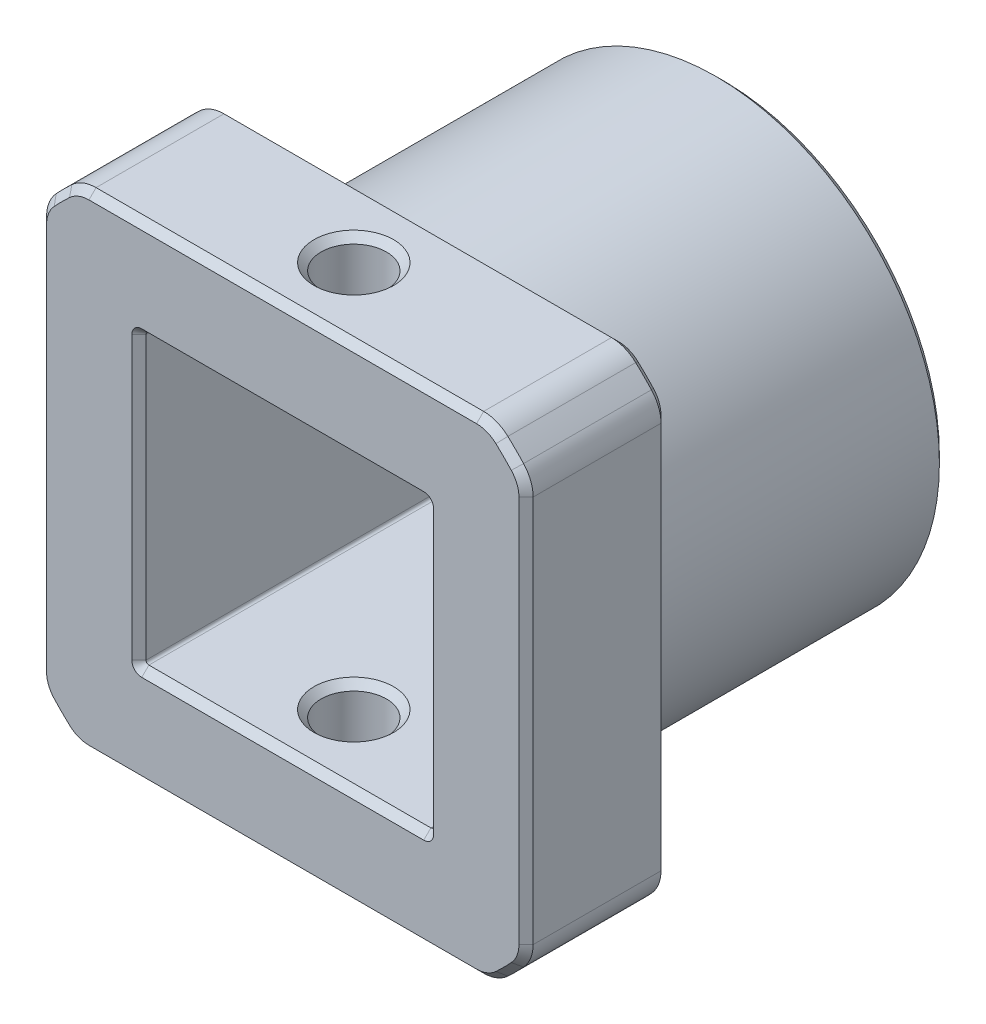
SolidWorks part; units mm, degrees
ref_plane "Front" through (0, 0, 0) normal (0, 0, 1) x (1, 0, 0)
ref_plane "Top" through (0, 0, 0) normal (0, 1, 0) x (1, 0, 0)
ref_plane "Right" through (0, 0, 0) normal (1, 0, 0) x (0, 0, -1)
sketch "Skizze1" plane through (0, 0, 0) normal (0, 0, 1) x (1, 0, 0)
  line L1 (-10.125, -10.125) -> (10.125, -10.125)
  line L2 (-10.125, -10.125) -> (-10.125, 10.125)
  line L3 (-10.125, 10.125) -> (10.125, 10.125)
  line L4 (10.125, -10.125) -> (10.125, 10.125)
  line L5 (-10.125, -10.125) -> (10.125, 10.125) construction
  line L6 (-10.125, 10.125) -> (10.125, -10.125) construction
  circle A0 centre (0, 0) radius 15.725
  point P0 (0, 0)
  dimension "D2" = 31.45
  dimension "D1" = 20.25
extrude "Aufsatz-Linear austragen1" add sketch "Skizze1" along normal blind 21
sketch "Skizze2" plane through (0, 0, 21) normal (0, 0, 1) x (1, 0, 0)
  line L0 (-14.594, 17.125) -> (14.594, 17.125)
  line L1 (-10.125, -10.125) -> (10.125, -10.125)
  line L2 (-10.125, -10.125) -> (-10.125, 10.125)
  line L3 (-10.125, 10.125) -> (10.125, 10.125)
  line L4 (10.125, -10.125) -> (10.125, 10.125)
  line L5 (-10.125, -10.125) -> (10.125, 10.125) construction
  line L6 (-10.125, 10.125) -> (10.125, -10.125) construction
  line L7 (0, 0) -> (13.8508, 0) construction
  line L8 (0, 0) -> (0, 13.2524) construction
  line L9 (17.125, -14.594) -> (17.125, 14.594)
  line L10 (14.594, -17.125) -> (-14.594, -17.125)
  line L11 (-17.125, 14.594) -> (-17.125, -14.594)
  arc A0 (-14.594, 17.125) -> (-17.125, 14.594) centre (0, 0) ccw
  arc A2 (-17.125, -14.594) -> (-14.594, -17.125) centre (0, 0) ccw
  arc A3 (14.594, -17.125) -> (17.125, -14.594) centre (0, 0) ccw
  arc A4 (17.125, 14.594) -> (14.594, 17.125) centre (0, 0) ccw
  dimension "D1" = 45
  dimension "D2" = 7
extrude "Aufsatz-Linear austragen2" add sketch "Skizze2" along normal blind 10
sketch "Skizze3" plane through (0, 17.125, 0) normal (0, 1, 0) x (1, 0, 0)
  line L0 (0, -21) -> (0, -31) construction
  line L2 (14.594, -31) -> (-14.594, -31) construction
  circle A0 centre (0, -26) radius 2.3
  dimension "D1" = 4.6
  dimension "D2" = 10
extrude "Schnitt-Linear austragen1" cut sketch "Skizze3" against normal through all
pattern_circular "Kreismuster1" [suppressed] count 2 over 90 reverse direction yes of bodies 103
fillet "Verrundung1" radius 0.2 4 edges at (10.125, -10.125, 15.5) (-10.125, -10.125, 15.5) (-10.125, 10.125, 15.5) (10.125, 10.125, 15.5)
fillet "Verrundung2" radius 2.5 8 edges at (-17.125, -14.594, 26) (-14.594, -17.125, 26) (14.594, -17.125, 26) (17.125, -14.594, 26) (17.125, 14.594, 26) (14.594, 17.125, 26) (-17.125, 14.594, 26) (-14.594, 17.125, 26)
chamfer "Fase1" distance 0.5 angle 45 37 edges at (-10.0664, -10.0664, 0) (-10.125, 0, 0) (-10.0664, 10.0664, 0) (0, 10.125, 0) (10.0664, 10.0664, 0) (10.125, 0, 0) (10.0664, -10.0664, 0) (0, -10.125, 0) (15.725, 0, 0) (-10.0664, 10.0664, 31) (-10.125, 0, 31) (-10.0664, -10.0664, 31) (0, -10.125, 31) (10.0664, -10.0664, 31) (10.125, 0, 31) (10.0664, 10.0664, 31) (0, 10.125, 31) (-16.951, 14.5586, 31) (-15.9099, 15.9099, 31) (-14.5586, 16.951, 31) (0, 17.125, 31) (14.5586, 16.951, 31) (15.9099, 15.9099, 31) (16.951, 14.5586, 31) (17.125, 0, 31) (16.951, -14.5586, 31) (15.9099, -15.9099, 31) (14.5586, -16.951, 31) (0, -17.125, 31) (-14.5586, -16.951, 31) (-15.9099, -15.9099, 31) (-16.951, -14.5586, 31) (-17.125, 0, 31) (0, -10.125, 28.3) (0, 10.125, 23.7) (0, -17.125, 28.3) (0, 17.125, 28.3)
chamfer "Fase2" [suppressed] distance 0.3 angle 45
chamfer "Fase3" [suppressed] distance 0.5 angle 45
chamfer "Fase4" distance 0.5 angle 45 16 edges at (0, -17.125, 21) (14.5586, -16.951, 21) (-14.5586, -16.951, 21) (15.9099, -15.9099, 21) (-15.9099, -15.9099, 21) (16.951, -14.5586, 21) (-16.951, -14.5586, 21) (17.125, 0, 21) (-17.125, 0, 21) (16.951, 14.5586, 21) (-16.951, 14.5586, 21) (15.9099, 15.9099, 21) (-15.9099, 15.9099, 21) (14.5586, 16.951, 21) (-14.5586, 16.951, 21) (0, 17.125, 21)
